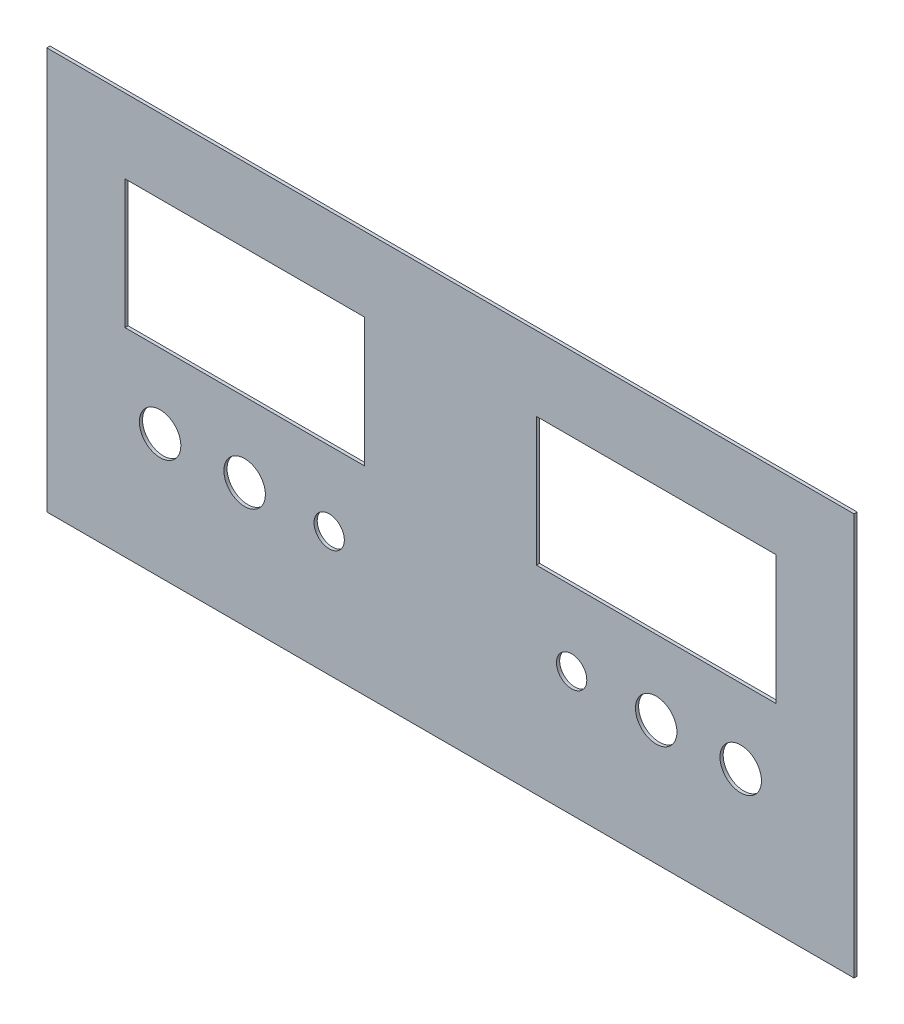
SolidWorks part; units mm, degrees
ref_plane "Front Plane" through (0, 0, 0) normal (0, 0, 1) x (1, 0, 0)
ref_plane "Top Plane" through (0, 0, 0) normal (0, 1, 0) x (1, 0, 0)
ref_plane "Right Plane" through (0, 0, 0) normal (1, 0, 0) x (0, 0, -1)
sketch "Sketch1" plane through (0, 0, 0) normal (0, 0, 1) x (1, 0, 0)
  line L1 (-126.5, 63) -> (126.5, 63)
  line L2 (-126.5, 63) -> (-126.5, -63)
  line L3 (-126.5, -63) -> (126.5, -63)
  line L4 (126.5, 63) -> (126.5, -63)
  line L5 (0, -63) -> (0, 63) construction
  line L6 (-126.5, 0) -> (126.5, 0) construction
  point P0 (0, 0)
  dimension "D1" = 126
  dimension "D2" = 253
base flange "Base-Flange1" sketch "Sketch1" thickness 1 reverse thickness direction no parameters "D1"=0.7366
sketch "Sketch2" plane through (0, 0, -1) normal (0, 0, -1) x (-1, 0, 0)
  line L0 (-64.5, 39) -> (-64.5, 39.7) construction
  line L1 (-29, 39) -> (-100, 39) construction
  line L2 (-100, 19.5) -> (-102, 19.5) construction
  line L3 (-100, 13.5) -> (-100, 25.5) construction
  line L4 (-29, 19.5) -> (-27, 19.5) construction
  line L5 (-29, 25.5) -> (-29, 13.5) construction
  line L6 (-64.5, 0) -> (-64.5, -0.7) construction
  line L7 (-54.5, 0) -> (-74.5, 0) construction
  line L8 (64.5, 39) -> (64.5, 39.7) construction
  line L9 (100, 39) -> (29, 39) construction
  line L10 (29, 19.5) -> (27, 19.5) construction
  line L11 (29, 39) -> (29, 0) construction
  line L12 (100, 19.5) -> (102, 19.5) construction
  line L13 (100, 0) -> (100, 39) construction
  line L14 (64.5, 0) -> (64.5, -0.7) construction
  line L15 (74.5, 0) -> (54.5, 0) construction
  line L17 (-102, 39.7) -> (-27, 39.7)
  line L18 (-102, 39.7) -> (-102, -0.7)
  line L19 (-102, -0.7) -> (-27, -0.7)
  line L20 (-27, 39.7) -> (-27, -0.7)
  line L21 (27, 39.7) -> (102, 39.7)
  line L22 (27, 39.7) -> (27, -0.7)
  line L23 (27, -0.7) -> (102, -0.7)
  line L24 (102, 39.7) -> (102, -0.7)
  circle A0 centre (-91, -24) radius 6.5
  circle A1 centre (-64.5, -24) radius 6.5
  circle A2 centre (64.5, -24) radius 6.5
  circle A3 centre (91, -24) radius 6.5
  circle A4 centre (-38, -24) radius 4.75
  circle A5 centre (38, -24) radius 4.75
  dimension "D9" = 13
  dimension "D10" = 13
  dimension "D11" = 13
  dimension "D12" = 13
  dimension "D13" = 9.5
  dimension "D14" = 9.5
  dimension "D1" = 0.7
  dimension "D2" = 2
  dimension "D3" = 2
  dimension "D4" = 0.7
  dimension "D5" = 0.7
  dimension "D6" = 0.7
  dimension "D7" = 2
  dimension "D8" = 2
extrude "Cut-Extrude1" cut sketch "Sketch2" against normal blind 10 normal cut yes
sketch "Bend-Lines1" [suppressed] plane through (0, 0, 0) normal (0, 1, 0) x (1, 0, 0)
sketch "Bounding-Box1" [suppressed] plane through (0, 0, 0) normal (0, 1, 0) x (1, 0, 0)
sheet metal parameters "Sheet-Metal1" thickness 1 parameters "D1"=0.7366
flat pattern "Flat-Pattern1" [suppressed]
sketch "Bend-Lines2" plane through (0, 0, 0) normal (0, 1, 0) x (1, 0, 0)
sketch3d "Bounding-Box2" [suppressed]
  line L0 (126.5, -63, 0) -> (-126.5, -63, 0) construction
  line L1 (126.5, 63, 0) -> (-126.5, 63, 0) construction
  line L2 (126.5, -63, 0) -> (126.5, 63, 0) construction
  line L3 (-126.5, -63, 0) -> (-126.5, 63, 0) construction
sheet metal parameters "Sheet-Metal2" thickness 1 parameters "D1"=0.7366
flat pattern "Flat-Pattern1"
sketch "Bend-Lines2" plane through (0, 0, 0) normal (0, 1, 0) x (1, 0, 0)
sketch3d "Bounding-Box2" [suppressed]
  line L0 (-126.5, -63, 0) -> (126.5, -63, 0) construction
  line L1 (-126.5, 63, 0) -> (126.5, 63, 0) construction
  line L2 (-126.5, -63, 0) -> (-126.5, 63, 0) construction
  line L3 (126.5, -63, 0) -> (126.5, 63, 0) construction
